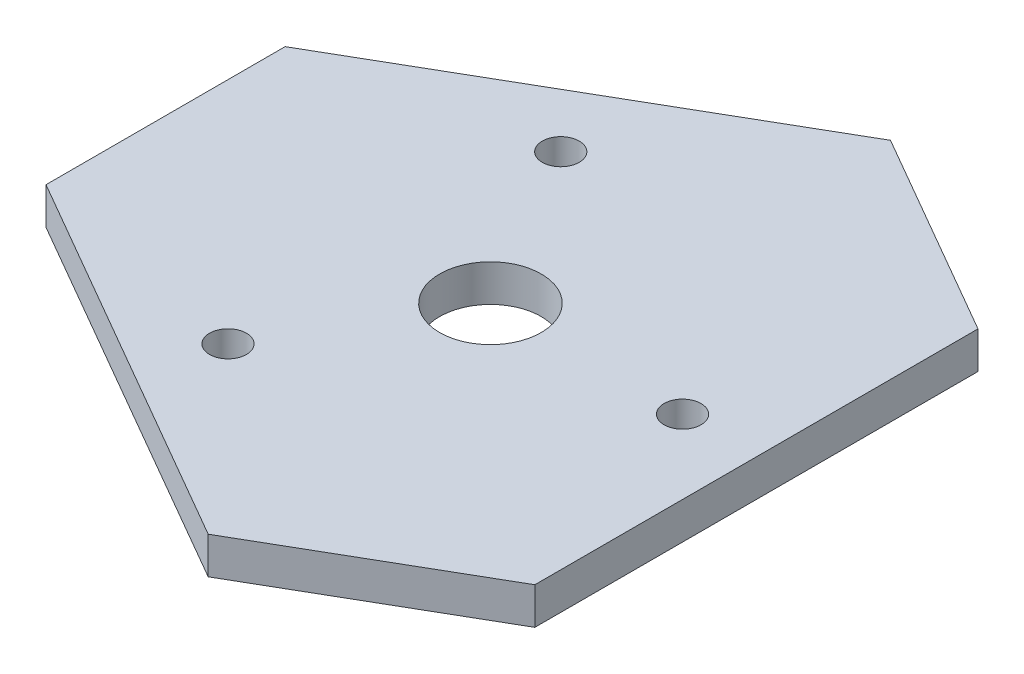
SolidWorks part; units mm, degrees
ref_plane "Front Plane" through (0, 0, 0) normal (0, 0, 1) x (1, 0, 0)
ref_plane "Top Plane" through (0, 0, 0) normal (0, 1, 0) x (1, 0, 0)
ref_plane "Right Plane" through (0, 0, 0) normal (1, 0, 0) x (0, 0, -1)
sketch "Sketch2" plane through (0, 0, 0) normal (0, 1, 0) x (1, 0, 0)
  line L0 (0, 0) -> (-43656.8426, 0) construction
  line L1 (22.8681, 19.05) -> (22.8681, -19.05)
  line L2 (22.8681, 39.6088) -> (-45.7363, 0) construction
  line L3 (-45.7363, 0) -> (22.8681, -39.6088) construction
  line L4 (22.8681, -39.6088) -> (22.8681, 39.6088) construction
  line L5 (22.8681, -19.05) -> (5.0637, -29.3294)
  line L6 (5.0637, -29.3294) -> (-27.9319, -10.2794)
  line L7 (-0.0355, 0.0615) -> (21828.3858, -37807.8732) construction
  line L8 (40.0162, 69.3101) -> (-21788.4051, -37738.6247) construction
  line L9 (-27.9319, -10.2794) -> (-27.9319, 10.2794)
  line L10 (-27.9319, 10.2794) -> (5.0637, 29.3294)
  line L11 (5.0637, 29.3294) -> (22.8681, 19.05)
  circle A0 centre (0, 0) radius 45.7363 construction
  circle A1 centre (16.5181, 0) radius 1.5875
  circle A2 centre (-8.2591, -14.3051) radius 1.5875
  circle A3 centre (-8.2591, 14.3051) radius 1.5875
  circle A4 centre (0, 0) radius 4.3656
  dimension "D2" = 3.175
  dimension "D3" = 8.7312
  dimension "D1" = 38.1
  dimension "D4" = 3
  dimension "D5" = 6.35
  dimension "D6" = 50.8
extrude "Boss-Extrude2" add sketch "Sketch2" along normal blind 3.175
